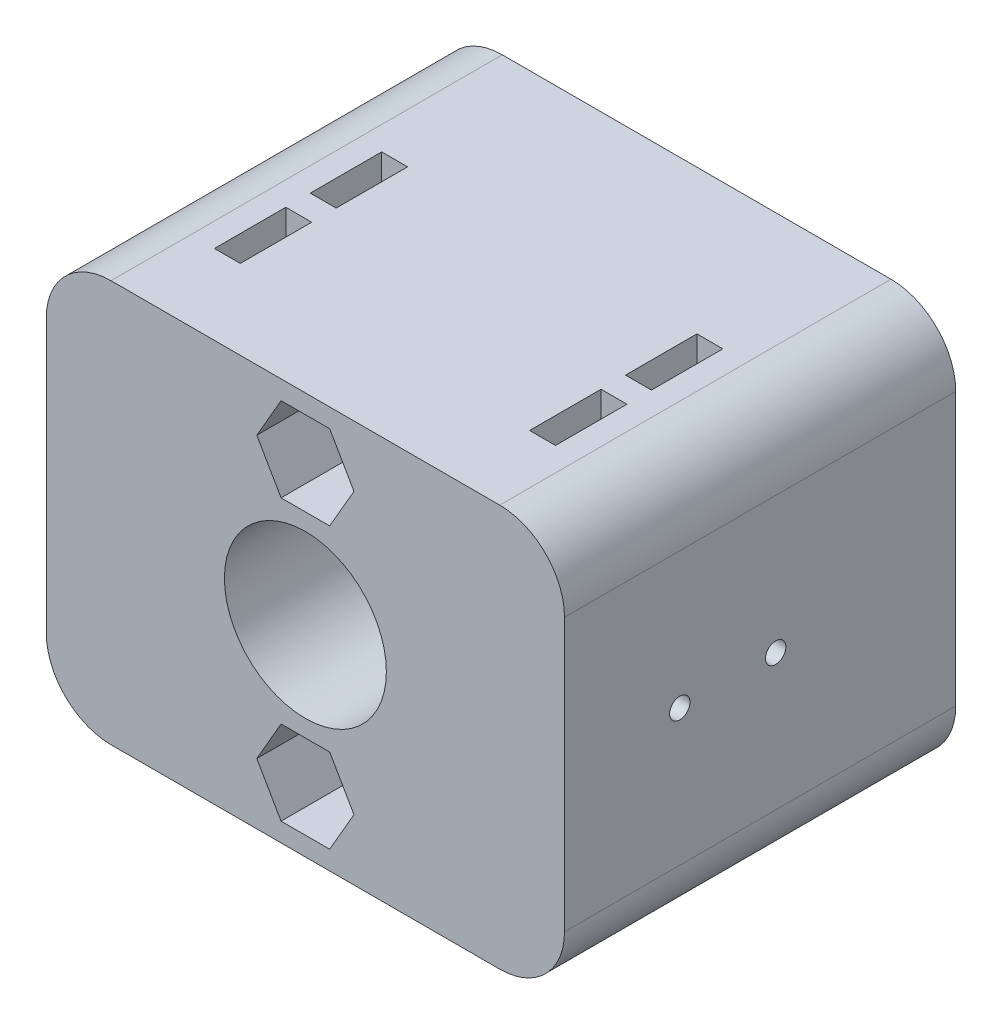
SolidWorks part; units mm, degrees
ref_plane "Front Plane" through (0, 0, 0) normal (0, 0, 1) x (1, 0, 0)
ref_plane "Top Plane" through (0, 0, 0) normal (0, 1, 0) x (1, 0, 0)
ref_plane "Right Plane" through (0, 0, 0) normal (1, 0, 0) x (0, 0, -1)
sketch "Sketch1" plane through (0, 0, 0) normal (0, 0, 1) x (1, 0, 0)
  line L0 (-82.55, -139.7) -> (-82.55, 139.7) construction
  line L1 (-82.55, 29.2453) -> (-31.75, 29.2453)
  line L2 (-82.55, 29.2453) -> (-82.55, -10.15)
  line L3 (-82.55, -10.15) -> (-31.75, -10.15)
  line L4 (-31.75, 29.2453) -> (-31.75, -10.15)
  line L5 (-82.55, 29.2453) -> (-31.75, -10.15) construction
  line L6 (-82.55, -10.15) -> (-31.75, 29.2453) construction
  line L7 (-31.75, -139.7) -> (-31.75, 139.7) construction
  arc A0 (-49.53, -8.6164) -> (-43.6698, -4.8149) centre (-57.15, 9.5476) ccw construction
  arc A1 (-64.77, 27.7117) -> (-70.6302, 23.9102) centre (-57.15, 9.5476) ccw construction
  circle A2 centre (-57.15, 23.27) radius 2.75
  circle A3 centre (-57.15, -4.1747) radius 2.75
  circle A4 centre (-57.15, -4.1747) radius 2.75 construction
  circle A5 centre (-57.15, 9.5476) radius 7.9375
  point P4 (-57.15, 9.5476)
  dimension "D1" = 15.875
extrude "Boss-Extrude1" add sketch "Sketch1" along normal up to surface (38.35 mm away) contours L4 L1 L2 L3 A3 A2 region at (-57.15, 28.6025, 0)
sketch "Sketch2" plane through (0, -10.15, 0) normal (0, -1, 0) x (-1, 0, 0)
  line L5 (44.45, -17.65) -> (38.95, -17.65) construction
  line L6 (71.33, -14.15) -> (73.87, -14.15)
  line L7 (42.97, -30.55) -> (40.43, -30.55)
  line L8 (42.97, -30.55) -> (42.97, -23.55)
  line L9 (42.97, -23.55) -> (40.43, -23.55)
  line L10 (40.43, -30.55) -> (40.43, -23.55)
  line L11 (42.97, -30.55) -> (40.43, -23.55) construction
  line L12 (42.97, -23.55) -> (40.43, -30.55) construction
  line L17 (20.2, -30.55) -> (5.2, -30.55) construction
  line L20 (40.43, -14.15) -> (42.97, -14.15)
  line L21 (40.43, -14.15) -> (40.43, -21.15)
  line L22 (40.43, -21.15) -> (42.97, -21.15)
  line L23 (42.97, -14.15) -> (42.97, -21.15)
  line L24 (40.43, -14.15) -> (42.97, -21.15) construction
  line L25 (40.43, -21.15) -> (42.97, -14.15) construction
  line L30 (71.33, -14.15) -> (71.33, -21.15)
  line L31 (71.33, -21.15) -> (73.87, -21.15)
  line L32 (73.87, -14.15) -> (73.87, -21.15)
  line L33 (71.33, -14.15) -> (73.87, -21.15) construction
  line L34 (71.33, -21.15) -> (73.87, -14.15) construction
  line L35 (73.87, -23.55) -> (71.33, -23.55)
  line L36 (73.87, -23.55) -> (73.87, -30.55)
  line L37 (73.87, -30.55) -> (71.33, -30.55)
  line L38 (71.33, -23.55) -> (71.33, -30.55)
  line L39 (73.87, -23.55) -> (71.33, -30.55) construction
  line L40 (73.87, -30.55) -> (71.33, -23.55) construction
  line L41 (38.95, -6.35) -> (38.95, -22.35) construction
  line L42 (44.45, -22.35) -> (44.45, -6.35) construction
  line L43 (5.2, -14.15) -> (20.2, -14.15) construction
  line L45 (5.2, -23.55) -> (20.2, -23.55) construction
  line L46 (69.85, -27.05) -> (75.35, -27.05) construction
  line L47 (75.35, -32) -> (75.35, 3.175) construction
  line L48 (69.85, 3.175) -> (69.85, -32) construction
  point P4 (72.6, -17.65)
  point P9 (41.7, -27.05)
  point P14 (72.6, -27.05)
  point P21 (41.7, -17.65)
  point P31 (41.7, -17.65)
  point P41 (72.6, -27.05)
  dimension "D1" = 2.54
extrude "Cut-Extrude1" cut sketch "Sketch2" against normal through all both and the other way through all contours L10 L7 L8 L9 | L32 L6 L30 L31 | L35 L38 L37 L36 | L23 L22 L21 L20 region at (-72.6, -10.15, 17.65) region at (-41.7, -10.15, 27.05) region at (-72.6, -10.15, 27.05)
sketch "Sketch3" plane through (-31.75, 0, 0) normal (1, 0, 0) x (0, 0, -1)
  line L0 (-23.55, 9.5476) -> (-30.55, 9.5476) construction
  line L1 (-30.55, 29.2453) -> (-30.55, -10.15) construction
  line L3 (-23.55, 29.2453) -> (-23.55, -10.15) construction
  line L4 (-38.35, -10.15) -> (-38.35, 29.2453) construction
  line L8 (-14.15, 29.2453) -> (-21.15, 29.2453) construction
  circle A0 centre (-27.05, 9.5476) radius 3.5
  circle A1 centre (-17.65, 9.5476) radius 1
  circle A3 centre (-27.05, 9.5476) radius 1
  point P7 (-27.05, 9.5476)
  point P17 (-38.35, 9.5476)
  point P18 (-17.65, 29.2453)
  dimension "D1" = 2
extrude "Cut-Extrude2" cut sketch "Sketch3" against normal through all both and the other way through all contours A3 | A1
fillet "Fillet1" radius 6.35 4 edges at (-82.55, -10.15, 19.175) (-82.55, 29.2453, 19.175) (-31.75, -10.15, 19.175) (-31.75, 29.2453, 19.175)
sketch "Sketch4" plane through (0, 0, 38.35) normal (0, 0, 1) x (1, 0, 0)
  line L0 (24.6066, -147) -> (19.8434, -147) construction
  line L1 (-52.3869, 23.2692) -> (-54.7677, 27.3946)
  line L2 (-54.7677, 27.3946) -> (-59.5309, 27.3954)
  line L3 (-59.5309, 27.3954) -> (-61.9131, 23.2708)
  line L4 (-61.9131, 23.2708) -> (-59.5323, 19.1454)
  line L5 (-59.5323, 19.1454) -> (-54.7691, 19.1446)
  line L6 (-54.7691, 19.1446) -> (-52.3869, 23.2692)
  line L7 (-52.3869, -4.1747) -> (-54.7684, -0.0497)
  line L8 (-54.7684, -0.0497) -> (-59.5316, -0.0497)
  line L9 (-59.5316, -0.0497) -> (-61.9131, -4.1747)
  line L10 (-61.9131, -4.1747) -> (-59.5316, -8.2997)
  line L11 (-59.5316, -8.2997) -> (-54.7684, -8.2997)
  line L12 (-54.7684, -8.2997) -> (-52.3869, -4.1747)
  circle A0 centre (-57.15, 23.27) radius 4.125 construction
  circle A1 centre (-57.15, -4.1747) radius 4.125 construction
extrude "Cut-Extrude3" cut sketch "Sketch4" against normal blind 6.35 contours L2 L3 L4 L5 L6 L1 | L11 L12 L7 L8 L9 L10
